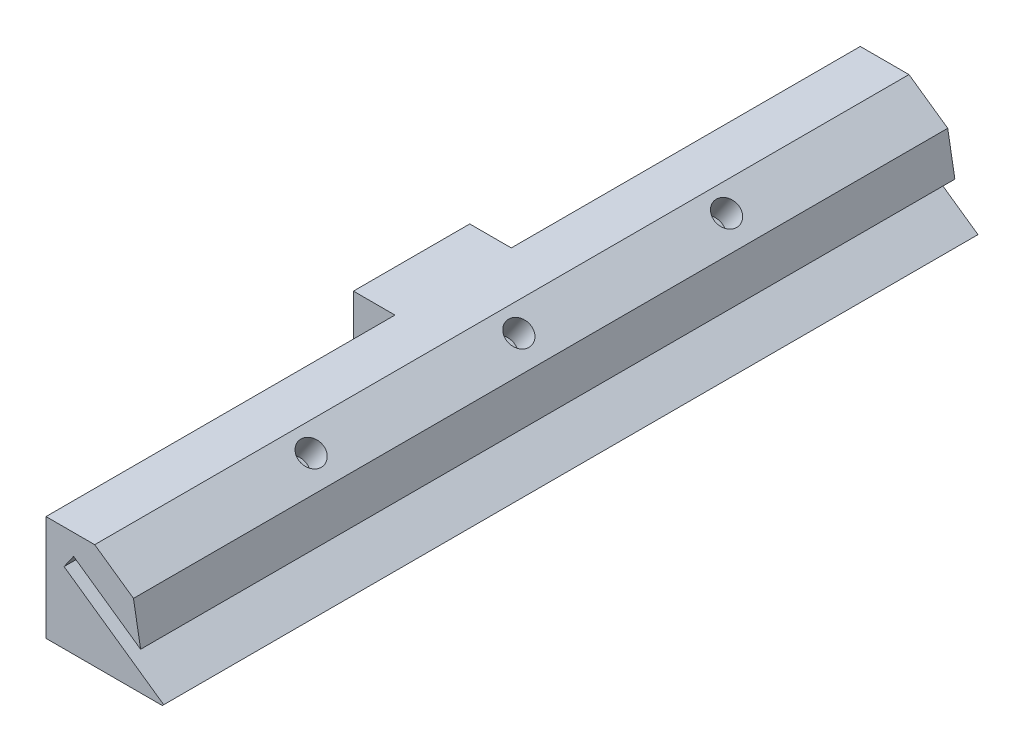
SolidWorks part; units mm, degrees
material "ABS"
ref_plane "Plano frontal" through (0, 0, 0) normal (0, 0, 1) x (1, 0, 0)
ref_plane "Plano superior" through (0, 0, 0) normal (0, 1, 0) x (1, 0, 0)
ref_plane "Plano direito" through (0, 0, 0) normal (1, 0, 0) x (0, 0, -1)
sketch "Esboço1" plane through (0, 0, 0) normal (0, 0, 1) x (1, 0, 0)
  line L1 (0, 0) -> (94, 0)
  line L5 (75.8625, 12.7) -> (0, 12.7)
  line L6 (0, 12.7) -> (0, 0)
  line L8 (75.8625, 12.7) -> (94, 0)
  dimension "D1" = 35
  dimension "D2" = 94
  dimension "D3" = 12.7
extrude "Ressalto-extrusão1" add sketch "Esboço1" along normal blind 98
sketch "Esboço4" plane through (0, 12.7, 0) normal (0, 1, 0) x (1, 0, 0)
  line L0 (75.8625, -98) -> (0, -98) construction
  line L5 (75.8625, 0) -> (0, 0) construction
  line L7 (33, -76) -> (33, -98)
  line L8 (33, -98) -> (0, -98)
  line L9 (0, -76) -> (0, -98)
  line L15 (33, 0) -> (0, 0)
  line L16 (33, 0) -> (33, -22)
  line L18 (0, 0) -> (0, -22)
  line L28 (0, -98) -> (0, 0) construction
  line L29 (70, -98) -> (37, -98)
  line L30 (70, -98) -> (70, -76)
  line L32 (37, -98) -> (37, -76)
  line L33 (70, 0) -> (37, 0)
  line L34 (70, 0) -> (70, -22)
  line L36 (37, 0) -> (37, -22)
  line L56 (70, -22) -> (37, -22)
  line L57 (33, -22) -> (0, -22)
  line L58 (0, -76) -> (33, -76)
  line L59 (37, -76) -> (70, -76)
  dimension "D1" = 22
  dimension "D3" = 33
  dimension "D4" = 22
  dimension "D5" = 33
  dimension "D6" = 22
  dimension "D7" = 22
  dimension "D8" = 4
  dimension "D9" = 33
  dimension "D10" = 4
  dimension "D11" = 33
  dimension "D12" = 22
  dimension "D19" = 22
  dimension "D21" = 22
  dimension "D23" = 22
extrude "Corte-extrusão3" cut sketch "Esboço4" against normal blind 25
sketch "Esboço10" plane through (0, 0, 76) normal (0, 0, 1) x (1, 0, 0)
  line L0 (16.5, 12.7) -> (16.5, 0) construction
  line L1 (33, 12.7) -> (0, 12.7) construction
  line L2 (33, 0) -> (0, 0) construction
  line L3 (53.5, 12.7) -> (53.5, 0) construction
  line L4 (37, 12.7) -> (33, 12.7) construction
  line L5 (35, 12.7) -> (35, 0) construction
  line L6 (33, 0) -> (37, 0) construction
  line L7 (10.5, 12.7) -> (22.5, 12.7)
  line L8 (10.5, 12.7) -> (10.5, 8.7)
  line L9 (10.5, 8.7) -> (22.5, 8.7)
  line L10 (22.5, 12.7) -> (22.5, 8.7)
  line L11 (47.5, 12.7) -> (47.5, 8.7)
  line L12 (59.5, 8.7) -> (47.5, 8.7)
  line L13 (59.5, 12.7) -> (59.5, 8.7)
  line L14 (59.5, 12.7) -> (47.5, 12.7)
  dimension "D1" = 4
  dimension "D2" = 6
  dimension "D3" = 6
extrude "Corte-extrusão8" cut sketch "Esboço10" against normal through all
sketch "Esboço11" plane through (0, 12.7, 0) normal (0, 1, 0) x (1, 0, 0)
  line L0 (0, -26.5) -> (29.25, -26.5) construction
  line L1 (0, -76) -> (0, -22) construction
  line L2 (29.25, -26.5) -> (29.25, -71.5) construction
  line L3 (29.25, -71.5) -> (0, -71.5) construction
  line L4 (0, -22) -> (10.5, -22) construction
  line L5 (10.5, -76) -> (0, -76) construction
  line L6 (40.75, -26.5) -> (66.25, -26.5) construction
  line L7 (66.25, -26.5) -> (66.25, -71.5) construction
  line L8 (66.25, -71.5) -> (40.75, -71.5) construction
  line L9 (47.5, -22) -> (47.5, -76) construction
  circle A0 centre (29.25, -26.5) radius 1.6
  circle A1 centre (29.25, -71.5) radius 1.6
  circle A2 centre (3.75, -71.5) radius 1.6
  circle A3 centre (3.75, -26.5) radius 1.6
  circle A4 centre (40.75, -26.5) radius 1.6
  circle A5 centre (66.25, -26.5) radius 1.6
  circle A6 centre (66.25, -71.5) radius 1.6
  circle A7 centre (40.75, -71.5) radius 1.6
  dimension "D6" = 3.2
  dimension "D7" = 3.2
  dimension "D8" = 3.2
  dimension "D9" = 3.2
  dimension "D13" = 3.2
  dimension "D14" = 3.2
  dimension "D15" = 3.2
  dimension "D16" = 3.2
  dimension "D1" = 4.5
  dimension "D2" = 4.5
  dimension "D3" = 3.75
  dimension "D4" = 3.75
  dimension "D5" = 25.5
  dimension "D10" = 6.75
  dimension "D11" = 25.5
  dimension "D12" = 6.75
  dimension "D17" = 45
extrude "Corte-extrusão9" cut sketch "Esboço11" against normal blind 20
sketch "Esboço12" plane through (0, 12.7, 0) normal (0, 1, 0) x (1, 0, 0)
  line L1 (46, -29) -> (24, -29)
  line L2 (46, -29) -> (46, -69)
  line L3 (46, -69) -> (24, -69)
  line L4 (24, -29) -> (24, -69)
  line L5 (33, -76) -> (22.5, -76) construction
  line L7 (47.5, -22) -> (47.5, -76) construction
  dimension "D1" = 1.5
  dimension "2" = 22
  dimension "D2" = 40
  dimension "D3" = 7
extrude "Corte-extrusão10" cut sketch "Esboço12" against normal blind 10
fillet "Filete1" radius 2.5 4 edges at (24, 7.7, 69) (24, 7.7, 29) (46, 7.7, 29) (46, 7.7, 69)
hole_wizard "Escareado para parafuso Allen sextavado escareado de M41" positions "Esboço13" profile "Esboço14" countersink size "M4" standard "ISO" end condition through all
sketch "Esboço13" plane through (0, 0, 0) normal (0, -1, 0) x (-1, 0, 0)
  circle A0 centre (-3.75, -71.5) radius 1.6 construction
  point P0 (-66.25, -71.5)
  point P3 (-66.25, -26.5)
  point P6 (-40.75, -26.5)
  point P9 (-29.25, -26.5)
  point P12 (-29.25, -71.5)
  point P15 (-40.75, -71.5)
  point P18 (-3.75, -71.5)
  point P21 (-3.75, -26.5)
  dimension "D1" = 45
  dimension "D2" = 25.5
  dimension "D3" = 25.5
  dimension "D4" = 11.5
  dimension "D5" = 62.5
sketch "Esboço14" plane through (66.25, 0, 71.5) normal (1, 0, 0) x (0, 0, -1)
  line L0 (0, 0) -> (0, 12.7)
  line L1 (0, 12.7) -> (2.15, 12.7)
  line L2 (2.15, 12.7) -> (2.15, 2.33)
  line L3 (2.15, 2.33) -> (4.48, 0)
  line L5 (4.48, 0) -> (0, 0)
  line L6 (-2.15, 2.33) -> (-4.48, 0) construction
  line L11 (0, -6.35) -> (0, 107.95) construction
  dimension "Thru Hole Dia." = 4.3
  dimension "Thru Hole Depth" = 12.7
  dimension "Near C'Sink Dia." = 8.96
  dimension "Near C'Sink Angle" = 90
sketch "Esboço15" plane through (0, 12.7, 0) normal (0, 1, 0) x (1, 0, 0)
  line L0 (33, -98) -> (33, -76) construction
  line L1 (37, 0) -> (33, 0)
  line L2 (37, 0) -> (37, -22)
  line L3 (37, -22) -> (33, -22)
  line L4 (33, 0) -> (33, -22)
  line L5 (37, -98) -> (33, -98)
  line L6 (37, -98) -> (37, -76)
  line L7 (37, -76) -> (33, -76)
  line L8 (33, -98) -> (33, -76)
extrude "Corte-extrusão11" cut sketch "Esboço15" against normal through all
sketch "Esboço16" plane through (0, 12.7, 0) normal (0, 1, 0) x (1, 0, 0)
  line L1 (70, -22) -> (0, -22)
  line L2 (70, -22) -> (70, -76)
  line L3 (70, -76) -> (0, -76)
  line L4 (0, -22) -> (0, -76)
  line L5 (70, -42) -> (65, -42)
  line L6 (70, -42) -> (70, -56)
  line L7 (70, -56) -> (65, -56)
  line L8 (65, -42) -> (65, -56)
  circle M4 centre (66.25, -71.5) radius 2.15
  circle M5 centre (66.25, -26.5) radius 2.15
  line M6 (70, -22) -> (59.5, -22)
  line M7 (59.5, -22) -> (59.5, -76)
  line M8 (59.5, -76) -> (70, -76)
  dimension "D1" = 20
  dimension "D2" = 5
  dimension "D3" = 14
extrude "Corte-extrusão12" cut sketch "Esboço16" against normal through all contours L1 L4 L3 M7 | L8 L5 L2 L7 M6 M7 M8 M5 M4 region at (64.2455, 12.7, 49) region at (29.75, 12.7, 49)
chamfer "Chanfro1" distance 10 angle 45 1 edges at (94, 0, 49) first distance on face at (73.2883, 0, 49)
ref_plane "Plano1" through (0, 0, 49) normal (0, 0, 1) x (1, 0, 0)
sketch "Esboço18" plane through (0, 0, 49) normal (0, 0, 1) x (1, 0, 0)
  line L0 (73.318, 10.209) -> (85.6053, 1.6053)
  line L1 (84, 0) -> (88.1184, 4.1184) construction
  line L2 (85.6053, 1.6053) -> (84.1693, 0.1693)
  line L3 (84.1693, 0.1693) -> (72.1709, 8.5707)
  line L4 (72.1709, 8.5707) -> (73.318, 10.209)
  line L5 (88.1184, 4.1184) -> (75.8625, 12.7) construction
  dimension "D1" = 2
  dimension "D2" = 3.5
  dimension "D3" = 15
extrude "Corte-extrusão14" cut sketch "Esboço18" against normal through all and the other way through all
chamfer "Chanfro2" distance 8 angle 55 1 edges at (88.1184, 4.1184, 49) first distance on face at (86.8618, 2.8618, 49)
sketch "Esboço19" plane through (30.9251, 44.1656, 0) normal (0.5736, 0.8192, 0) x (0.8192, -0.5736, 0)
  line L1 (45.9605, -42) -> (45.9605, -56) construction
  line L2 (54.8585, -98) -> (54.8585, 0) construction
  circle A0 centre (57.3585, -74) radius 1.5
  circle A1 centre (57.3585, -49) radius 1.5
  circle A2 centre (57.3585, -24) radius 1.5
  point P6 (57.0673, -49.2084)
  point P9 (45.9605, -49)
  point P12 (0, 0)
  dimension "D1" = 3
  dimension "D2" = 25
  dimension "D3" = 25
  dimension "D4" = 2.5
extrude "Corte-extrusão15" cut sketch "Esboço19" against normal up to next
